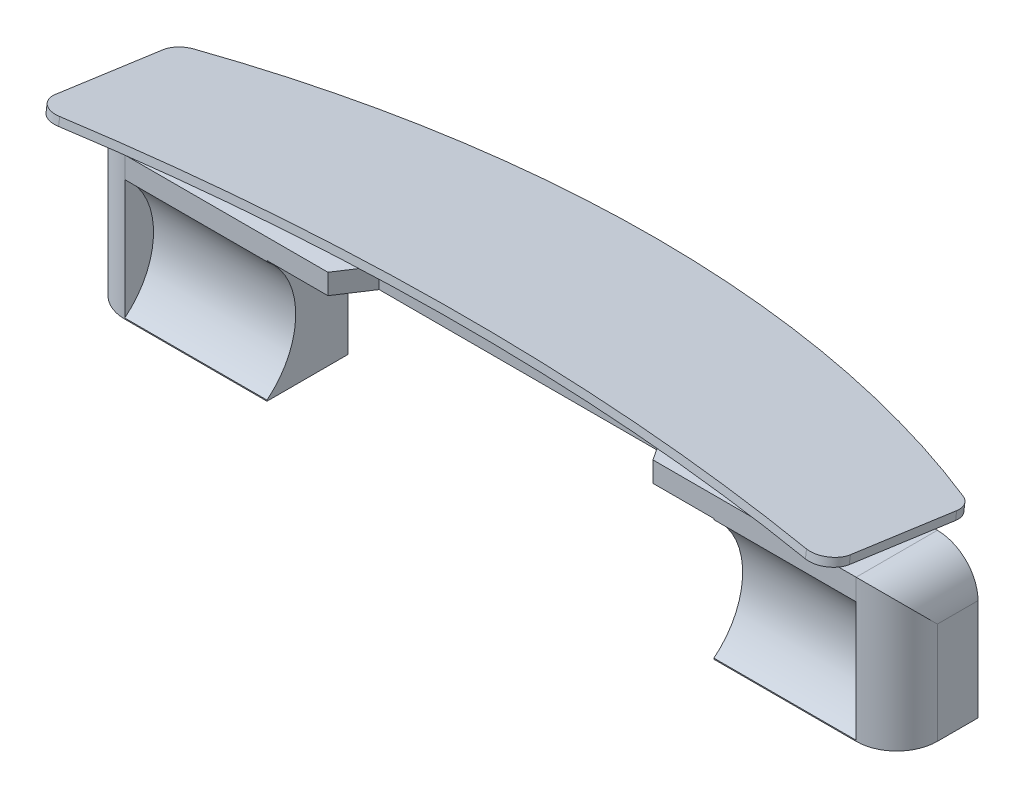
SolidWorks part; units mm, degrees
ref_plane "Front Plane" through (0, 0, 0) normal (0, 0, 1) x (1, 0, 0)
ref_plane "Top Plane" through (0, 0, 0) normal (0, 1, 0) x (1, 0, 0)
ref_plane "Right Plane" through (0, 0, 0) normal (1, 0, 0) x (0, 0, -1)
sketch "Sketch1" plane through (0, 0, 0) normal (0, 1, 0) x (1, 0, 0)
  line L0 (-77.5, 0) -> (77.5, 0) construction
  line L1 (-55, -10) -> (-100, -10)
  line L2 (-55, -10) -> (-55, 10)
  line L3 (-55, 10) -> (-100, 10)
  line L4 (-100, -10) -> (-100, 10)
  line L5 (-55, -10) -> (-100, 10) construction
  line L6 (-55, 10) -> (-100, -10) construction
  line L7 (0, -55) -> (0, 55) construction
  line L8 (55, 10) -> (100, -10) construction
  line L9 (55, -10) -> (100, 10) construction
  line L10 (100, -10) -> (100, 10)
  line L11 (55, 10) -> (100, 10)
  line L12 (55, -10) -> (55, 10)
  line L13 (55, -10) -> (100, -10)
  point P0 (-77.5, 0)
  point P7 (77.5, 0)
  point P15 (0, 0)
  dimension "D1" = 100
  dimension "D2" = 20
  dimension "D3" = 45
extrude "Boss-Extrude1" add sketch "Sketch1" along normal blind 30
sketch "Sketch2" plane through (0, 0, 0) normal (1, 0, 0) x (0, 0, -1)
  line L0 (-21.8388, 15) -> (-10, 15) construction
  line L1 (-10, 30) -> (-10, 0) construction
  circle A0 centre (-21.8388, 15) radius 18.9123
extrude "Cut-Extrude1" cut sketch "Sketch2" against normal blind 90 and the other way blind 90
sketch "Sketch4" plane through (0, 30, 0) normal (0, 1, 0) x (1, 0, 0)
  line L1 (-100, 10) -> (100, 10)
  line L2 (-100, 10) -> (-100, -10)
  line L3 (-100, -10) -> (100, -10)
  line L4 (100, 10) -> (100, -10)
extrude "Boss-Extrude2" add sketch "Sketch4" along normal blind 5
fillet "Fillet1" radius 10 4 edges at (-100, 35, 0) (100, 35, 0) (100, 17.5, 10) (-100, 17.5, 10)
sketch "Sketch5" plane through (0, 35, 0) normal (0, 1, 0) x (1, 0, 0)
  line L1 (-78, 6.0883) -> (-75, 6.0883)
  line L2 (-78, 6.0883) -> (-78, -7.1755)
  line L3 (-78, -7.1755) -> (-75, -7.1755)
  line L4 (-75, 6.0883) -> (-75, -7.1755)
  line L5 (75, 6.0883) -> (78, 6.0883)
  line L6 (75, 6.0883) -> (75, -7.1755)
  line L7 (75, -7.1755) -> (78, -7.1755)
  line L8 (78, 6.0883) -> (78, -7.1755)
  dimension "D1" = 75
  dimension "D2" = 75
  dimension "D3" = 3
  dimension "D4" = 3
extrude "Boss-Extrude3" add sketch "Sketch5" along normal blind 10
chamfer "Chamfer1" distance 15 angle 8 2 edges at (-76.5, 45, -6.0883) (76.5, 45, -6.0883) first distance on face at (-76.5, 45, 0.5436) first distance on face at (76.5, 45, 0.5436)
sketch "Sketch6" plane through (0, 42.9002, -6.0292) normal (0, 0.9903, -0.1392) x (1, 0, 0)
  line L0 (-78, -13.3345) -> (-78, 0.0597) construction
  line L2 (-98, 4.4411) -> (-98, -31.705)
  line L4 (98, 3.6905) -> (98, -32.0451)
  line L5 (78, -11.9767) -> (78, 1.158) construction
  arc A0 (-98, 4.4411) -> (98, 3.6905) centre (-0.8289, -212.3848) cw
  arc A1 (-98, -31.705) -> (98, -32.0451) centre (-0.8392, -515.5124) cw
  dimension "D1" = 20
  dimension "D2" = 20
extrude "Boss-Extrude4" add sketch "Sketch6" along normal blind 2
fillet "Fillet2" radius 5 4 edges at (-98, 43.2724, -10.5662) (98, 43.3768, -9.823) (98, 48.3503, 25.5648) (-98, 48.3029, 25.228)
sketch "Sketch7" plane through (0, 35, 0) normal (0, 1, 0) x (1, 0, 0)
  line L0 (-40, -10) -> (-35, -2.3979)
  line L1 (-90, -10) -> (90, -10) construction
  line L2 (-35, -2.3979) -> (35, -2.3979)
  line L3 (35, -2.3979) -> (40, -10)
  line L4 (40, -10) -> (-40, -10)
  dimension "D1" = 35
  dimension "D2" = 35
  dimension "D3" = 40
  dimension "D4" = 40
extrude "Cut-Extrude2" cut sketch "Sketch7" against normal through all
